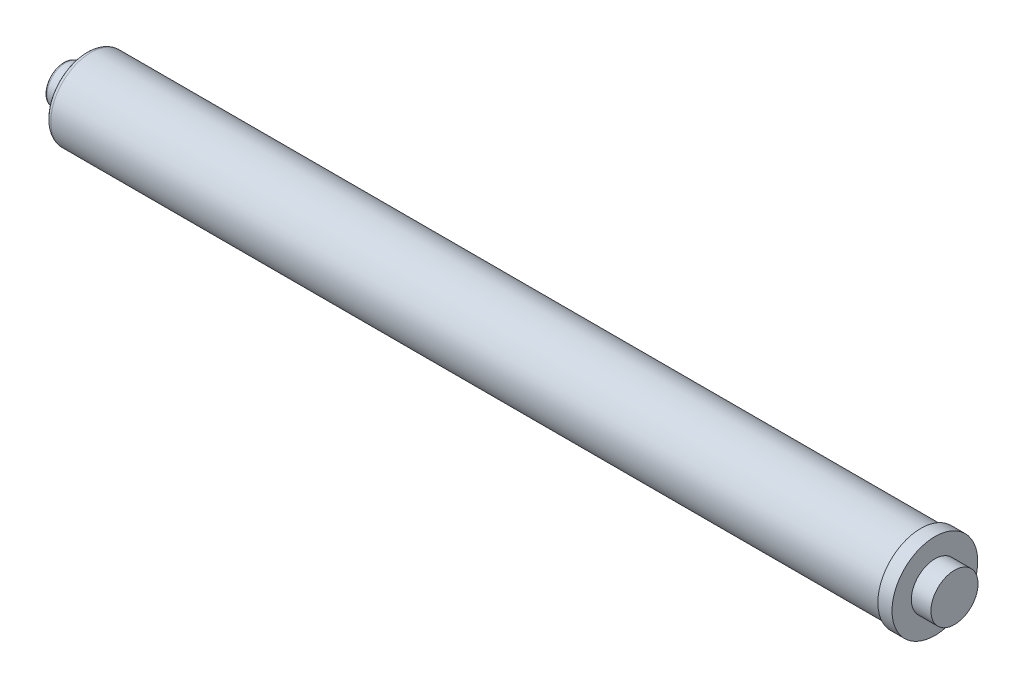
SolidWorks part; units mm, degrees
material "1060 Alloy"
ref_plane "Front Plane" through (0, 0, 0) normal (0, 0, 1) x (1, 0, 0)
ref_plane "Top Plane" through (0, 0, 0) normal (0, 1, 0) x (1, 0, 0)
ref_plane "Right Plane" through (0, 0, 0) normal (1, 0, 0) x (0, 0, -1)
sketch "Sketch1" plane through (0, 0, 0) normal (0, 1, 0) x (1, 0, 0)
  line L0 (-319.5622, 0) -> (364.5245, 0)
  line L1 (281.178, -26.9875) -> (-278.003, -26.9875)
  line L2 (281.178, -26.9875) -> (281.178, 26.9875)
  line L3 (281.178, 26.9875) -> (-278.003, 26.9875)
  line L4 (-281.178, -23.8125) -> (-281.178, 23.8125)
  line L5 (281.178, -26.9875) -> (-281.178, 26.9875) construction
  line L6 (281.178, 26.9875) -> (-281.178, -26.9875) construction
  line L8 (290.703, -28.8925) -> (281.178, -28.8925)
  line L9 (290.703, -28.8925) -> (290.703, 28.8925)
  line L10 (290.703, 28.8925) -> (281.178, 28.8925)
  line L11 (281.178, -28.8925) -> (281.178, 28.8925)
  line L12 (290.703, -28.8925) -> (281.178, 28.8925) construction
  line L13 (290.703, 28.8925) -> (281.178, -28.8925) construction
  line L14 (303.911, -15.875) -> (290.703, -15.875)
  line L15 (303.911, -15.875) -> (303.911, 15.875)
  line L16 (303.911, 15.875) -> (290.703, 15.875)
  line L17 (290.703, -15.875) -> (290.703, 15.875)
  line L18 (303.911, -15.875) -> (290.703, 15.875) construction
  line L19 (303.911, 15.875) -> (290.703, -15.875) construction
  line L20 (-294.8305, -12.7) -> (-281.178, -12.7)
  line L21 (-296.418, -11.1125) -> (-296.418, 11.1125)
  line L22 (-294.8305, 12.7) -> (-281.178, 12.7)
  line L23 (-281.178, -12.7) -> (-281.178, 12.7)
  line L24 (-296.418, -12.7) -> (-281.178, 12.7) construction
  line L25 (-296.418, 12.7) -> (-281.178, -12.7) construction
  arc A0 (-278.003, -26.9875) -> (-281.178, -23.8125) centre (-278.003, -23.8125) cw
  arc A1 (-278.003, 26.9875) -> (-281.178, 23.8125) centre (-278.003, 23.8125) ccw
  arc A2 (-294.8305, -12.7) -> (-296.418, -11.1125) centre (-294.8305, -11.1125) cw
  arc A3 (-296.418, 11.1125) -> (-294.8305, 12.7) centre (-294.8305, 11.1125) cw
  point P0 (0, 0)
  point P8 (285.9405, 0)
  point P13 (297.307, 0)
  point P18 (-288.798, 0)
  dimension "D9" = 3.175
  dimension "D10" = 1.5875
  dimension "D1" = 562.356
  dimension "D2" = 9.525
  dimension "D3" = 53.975
  dimension "D4" = 57.785
  dimension "D5" = 31.75
  dimension "D6" = 13.208
  dimension "D7" = 15.24
  dimension "D8" = 25.4
revolve "Revolve1" add sketch "Sketch1" angle 360 about L0 region at (-288.7776, 0, -6.3332) region at (0.04, 0, -13.4919) region at (285.9405, 0, -14.4463) region at (297.307, 0, -7.9375)
